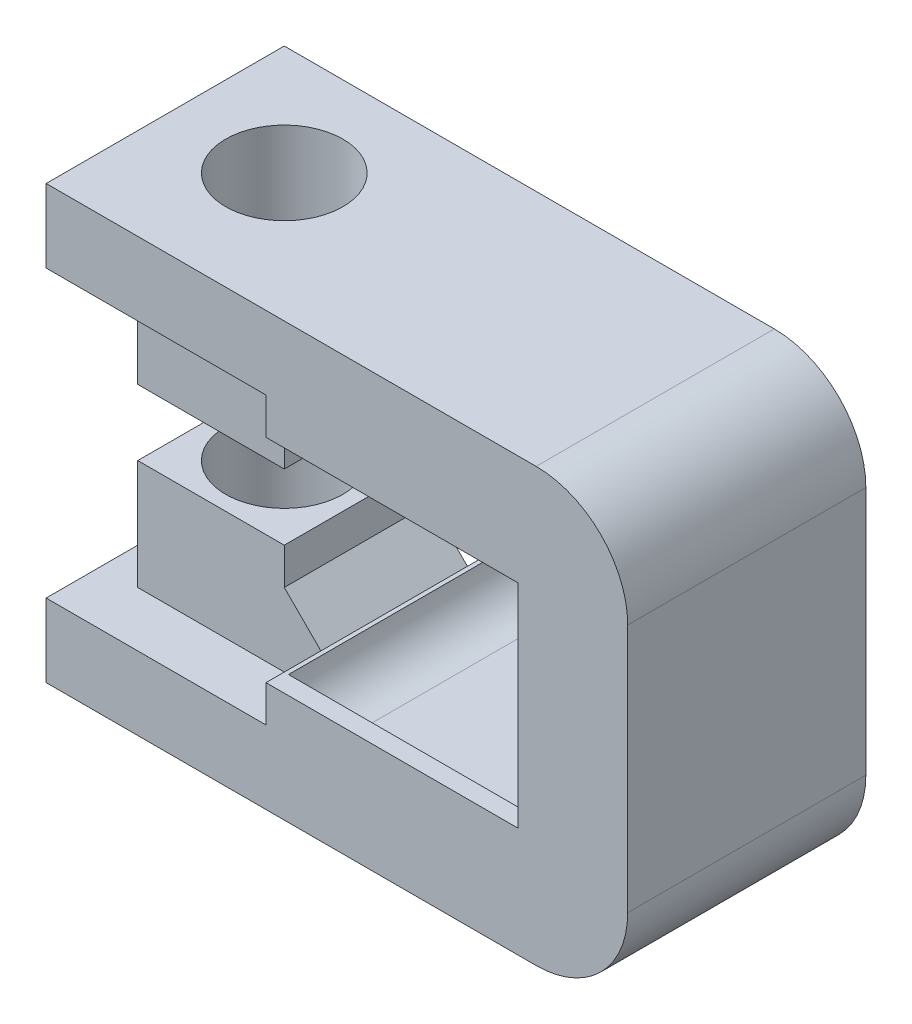
SolidWorks part; units mm, degrees
note: The reader was unsure of these and kept them because the rebuilt part matched: shared geometry of "草图1<3>", "草图2<2>", "草图2<4>", "草图2<5>".
ref_plane "前视基准面" through (0, 0, 0) normal (0, 0, 1) x (1, 0, 0)
ref_plane "上视基准面" through (0, 0, 0) normal (0, 1, 0) x (1, 0, 0)
ref_plane "右视基准面" through (0, 0, 0) normal (1, 0, 0) x (0, 0, -1)
other "Configuration Table"
sketch "草图1" plane through (0, 0, 0) normal (0, 0, 1) x (1, 0, 0)
  line L0 (-19.95, -7.8) -> (7.8, -7.8)
  line L1 (7.8, -7.8) -> (7.8, 7.8)
  line L2 (7.8, 7.8) -> (-19.95, 7.8)
  line L3 (-7.95, 7.8) -> (-7.95, -7.8) construction
  line L4 (-7.95, -5.8) -> (5.8, -5.8)
  line L5 (5.8, -5.8) -> (5.8, 5.8)
  line L7 (5.8, 5.8) -> (-7.95, 5.8)
  line L9 (-19.95, -11.8) -> (11.8, -11.8)
  line L10 (11.8, -11.8) -> (11.8, 11.8)
  line L11 (11.8, 11.8) -> (-19.95, 11.8)
  line L12 (-5.15, -5.15) -> (-5.15, -1.625)
  line L13 (-5.4, -1.375) -> (-7.4, -1.375)
  line L14 (-7.65, -1.625) -> (-7.65, -5.15)
  line L15 (-5.15, -7.65) -> (5.15, -7.65)
  line L16 (7.65, -5.15) -> (7.65, 5.15)
  line L17 (5.15, 7.65) -> (-5.15, 7.65)
  line L18 (-7.65, 5.15) -> (-7.65, 1.625)
  line L19 (-7.4, 1.375) -> (-5.4, 1.375)
  line L20 (-5.15, 1.625) -> (-5.15, 5.15)
  line L21 (-5.15, 5.15) -> (5.15, 5.15)
  line L22 (5.15, 5.15) -> (5.15, -5.15)
  line L23 (5.15, -5.15) -> (-5.15, -5.15)
  line L24 (-5.15, -5.15) -> (-5.15, -1.625) construction
  line L25 (-5.4, -1.375) -> (-7.4, -1.375) construction
  line L26 (-7.65, -1.625) -> (-7.65, -5.15) construction
  line L27 (-7.95, -7.65) -> (7.65, -7.65) construction
  line L28 (7.65, -7.65) -> (7.65, 5.15) construction
  line L29 (5.15, 7.65) -> (-5.15, 7.65) construction
  line L30 (-7.65, 5.15) -> (-7.65, 1.625) construction
  line L31 (-7.4, 1.375) -> (-5.4, 1.375) construction
  line L32 (-5.15, 1.625) -> (-5.15, 5.15) construction
  line L33 (-5.15, 5.15) -> (5.15, 5.15) construction
  line L34 (5.15, 5.15) -> (5.15, -5.15) construction
  line L35 (5.15, -5.15) -> (-5.15, -5.15) construction
  line L36 (-19.95, 7.8) -> (-19.95, 11.8)
  line L37 (-19.95, -7.8) -> (-19.95, -11.8)
  line L38 (-7.95, -5.8) -> (-7.95, -7.8)
  line L39 (-7.95, 5.8) -> (-7.95, 7.8)
  line L40 (-5.15, -7.65) -> (5.15, -7.65) construction
  arc A4 (-5.15, -1.625) -> (-5.4, -1.375) centre (-5.4, -1.625) ccw
  arc A5 (-7.4, -1.375) -> (-7.65, -1.625) centre (-7.4, -1.625) ccw
  arc A6 (-7.65, 1.625) -> (-7.4, 1.375) centre (-7.4, 1.625) ccw
  arc A7 (-5.4, 1.375) -> (-5.15, 1.625) centre (-5.4, 1.625) ccw
  arc A8 (-5.15, -1.625) -> (-5.4, -1.375) centre (-5.4, -1.625) ccw construction
  arc A9 (-7.4, -1.375) -> (-7.65, -1.625) centre (-7.4, -1.625) ccw construction
  arc A10 (-7.65, 1.625) -> (-7.4, 1.375) centre (-7.4, 1.625) ccw construction
  arc A11 (-5.4, 1.375) -> (-5.15, 1.625) centre (-5.4, 1.625) ccw construction
  arc A16 (-7.719, -5.8) -> (-5.15, -7.8) centre (-5.15, -5.15) ccw
  arc A17 (7.8, -5.15) -> (5.15, -7.8) centre (5.15, -5.15) cw
  arc A18 (5.15, 7.8) -> (7.8, 5.15) centre (5.15, 5.15) cw
  arc A19 (-5.15, 7.8) -> (-7.719, 5.8) centre (-5.15, 5.15) ccw
  arc A24 (5.15, -7.65) -> (7.65, -5.15) centre (5.15, -5.15) ccw
  arc A25 (5.15, -7.65) -> (7.65, -5.15) centre (5.15, -5.15) ccw
  arc A26 (7.65, 5.15) -> (5.15, 7.65) centre (5.15, 5.15) ccw
  arc A27 (7.65, 5.15) -> (5.15, 7.65) centre (5.15, 5.15) ccw
  arc A28 (-5.15, 7.65) -> (-7.65, 5.15) centre (-5.15, 5.15) ccw
  arc A29 (-5.15, 7.65) -> (-7.65, 5.15) centre (-5.15, 5.15) ccw
  arc A30 (-7.65, -5.15) -> (-5.15, -7.65) centre (-5.15, -5.15) ccw
  arc A31 (-7.65, -5.15) -> (-5.15, -7.65) centre (-5.15, -5.15) ccw
  point P23 (-5.15, -7.8)
  point P47 (-7.719, -5.8)
  point P50 (0, 0)
  dimension "D10" = 12
  dimension "D2" = 0.15
  dimension "D3" = 0.15
  dimension "D4" = 0.15
  dimension "D5" = 0.3
  dimension "D6" = 4
  dimension "D7" = 2
  dimension "D8" = 2
  dimension "D9" = 2
  dimension "D1" = 0
extrude "凸台-拉伸1" add sketch "草图1" against normal blind 12 contours L0 L37 L9 L10 L11 L36 L2 L1 | A19 L2 L39 L7 | A16 L4 L38 L0 | L1 A17 L0 | L2 A18 L1
extrude "凸台-拉伸2" add sketch "草图1<3>" along normal blind 1
sketch "草图1<3>" plane through (0, 0, 0) normal (0, 0, 1) x (1, 0, 0) same geometry as "草图1"
sketch "草图2" plane through (0, -11.8, 0) normal (0, -1, 0) x (1, 0, 0)
  line L0 (11.8, 0) -> (-19.95, 0) construction
  line L1 (11.8, -12) -> (11.8, 1) construction
  line L2 (-19.95, -12) -> (-19.95, 1) construction
  line L3 (11.8, -12) -> (-19.95, 0) construction
  line L4 (-19.95, -12) -> (11.8, 0) construction
  line L5 (11.8, -6) -> (-19.95, -6) construction
  line L6 (-7.95, -12) -> (-7.95, 1) construction
  line L7 (-7.95, -12) -> (-7.95, 1) construction
  line L10 (-9.95, -2) -> (-7.95, -2)
  line L11 (-17.95, -2) -> (-9.95, -2)
  line L12 (-17.95, -2) -> (-17.95, -10)
  line L13 (-17.95, -10) -> (-9.95, -10)
  line L14 (-9.95, -2) -> (-9.95, -10)
  line L16 (-17.95, -6) -> (-9.95, -6) construction
  line L17 (-9.95, -2) -> (-9.95, -10)
  line L20 (-7.95, -2) -> (-7.95, -10)
  line L21 (-7.95, -10) -> (-9.95, -10)
  circle A0 centre (-13.95, -6) radius 3.2
  point P14 (-4.075, -6)
  dimension "D1" = 6.4
  dimension "D2" = 6
  dimension "D3" = 8
  dimension "D4" = 4
  dimension "D5" = 4
extrude "凸台-拉伸3" add sketch "草图2" against normal blind 10 contours L14 L11 L12 L13 A0
extrude "切除-拉伸2" cut sketch "草图2<2>" against normal up to next contours A0
sketch "草图2<2>" plane through (0, -11.8, 0) normal (0, -1, 0) x (1, 0, 0) same geometry as "草图2"
extrude "凸台-拉伸4" add sketch "草图2<4>" against normal up to surface (6 mm away) contours L21 L20 L10 L14 up to face at (-3.2897, -5.8, -3.6667)
sketch "草图2<4>" plane through (0, -11.8, 0) normal (0, -1, 0) x (1, 0, 0) same geometry as "草图2"
chamfer "倒角1" distance 2 angle 45 1 edges at (-9.95, -5.8, -6)
mirror "镜向6" about plane through (0, 0, 0) normal (0, 1, 0) of "切除-拉伸2", "凸台-拉伸3"
extrude "凸台-拉伸5" add sketch "草图2<5>" against normal up to surface (2 mm away) from surface contours L21 L20 L10 L14
sketch "草图2<5>" plane through (0, -11.8, 0) normal (0, -1, 0) x (1, 0, 0) same geometry as "草图2"
chamfer "倒角2" distance 2 angle 45 1 edges at (-9.95, 5.8, -6)
fillet "圆角1" radius 5 2 edges at (11.8, -11.8, -5.5) (11.8, 11.8, -5.5)
